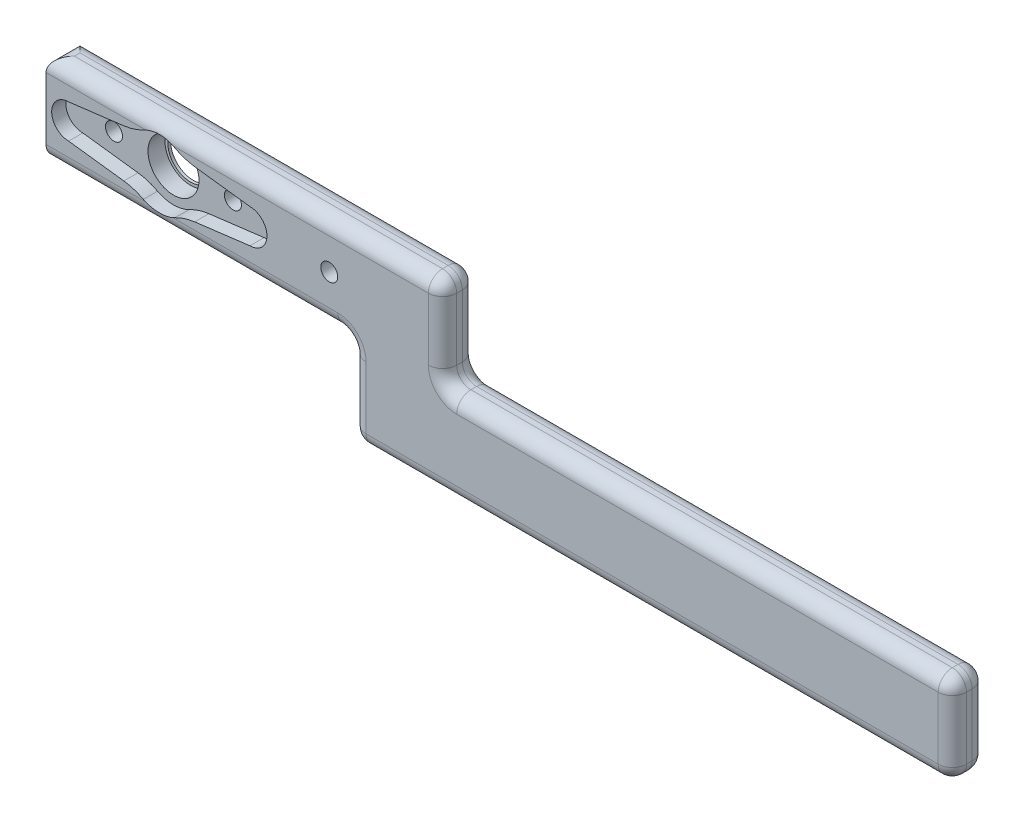
SolidWorks part; units mm, degrees
ref_plane "Спереди" through (0, 0, 0) normal (0, 0, 1) x (1, 0, 0)
ref_plane "Сверху" through (0, 0, 0) normal (0, 1, 0) x (1, 0, 0)
ref_plane "Справа" through (0, 0, 0) normal (1, 0, 0) x (0, 0, -1)
other "Configuration Table"
sketch "Эскиз1" plane through (0, 0, 0) normal (0, 0, 1) x (1, 0, 0)
  line L0 (20, 8) -> (20, 0) construction
  line L2 (0, 0) -> (0, 16)
  line L7 (9.5, 8) -> (0, 8) construction
  line L13 (160, -16) -> (160, 0)
  line L14 (70, 0) -> (160, 0)
  line L15 (54, -16) -> (160, -16)
  line L16 (54, 0) -> (54, -16)
  line L17 (70, 16) -> (70, 0)
  line L18 (0, 16) -> (70, 16)
  line L19 (0, 0) -> (54, 0)
  circle A0 centre (20, 8) radius 1.5
  circle A1 centre (30.5, 8) radius 1.5
  circle A2 centre (9.5, 8) radius 1.5
  dimension "D2" = 3
  dimension "D1" = 70
  dimension "D3" = 20
  dimension "D4" = 21
  dimension "D5" = 90
  dimension "D6" = 16
  dimension "D7" = 16
  dimension "D8" = 16
  dimension "D9" = 54
  dimension "D10" = 106
  dimension "D11" = 16
  dimension "D12" = 90
extrude "Бобышка-Вытянуть1" add sketch "Эскиз1" along normal blind 6
sketch "Эскиз4" plane through (0, 0, 6) normal (0, 0, 1) x (1, 0, 0)
  line L0 (20, 8) -> (20, -10.1424) construction
  line L1 (20, 8) -> (25.9044, 8) construction
  line L2 (4, 11) -> (13.7467, 12.2152)
  line L3 (4, 5) -> (13.7467, 3.7848)
  line L4 (36, 11) -> (26.2533, 12.2152)
  line L5 (36, 5) -> (26.2533, 3.7848)
  arc A0 (17.1911, 2.6981) -> (22.8089, 2.6981) centre (20, 8) ccw
  arc A1 (4, 11) -> (4, 5) centre (4, 8) ccw
  arc A2 (36, 11) -> (36, 5) centre (36, 8) cw
  arc A3 (22.8089, 13.3019) -> (17.1911, 13.3019) centre (20, 8) ccw
  arc A4 (13.7467, 3.7848) -> (17.1911, 2.6981) centre (12.5095, -6.1383) cw
  arc A5 (26.2533, 3.7848) -> (22.8089, 2.6981) centre (27.4905, -6.1383) ccw
  arc A6 (26.2533, 12.2152) -> (22.8089, 13.3019) centre (27.4905, 22.1383) cw
  arc A7 (13.7467, 12.2152) -> (17.1911, 13.3019) centre (12.5095, 22.1383) ccw
  point P1 (1, 8)
  point P4 (39, 8)
  point P18 (16.0314, 3.5)
  point P21 (23.9686, 3.5)
  point P24 (23.9686, 12.5)
  point P27 (16.0314, 12.5)
  dimension "D1" = 12
  dimension "D2" = 6
  dimension "D5" = 10
  dimension "D3" = 38
  dimension "D4" = 9
extrude "Вырез-Вытянуть3" cut sketch "Эскиз4" against normal blind 2.5
sketch "Эскиз5" plane through (0, 0, 3.5) normal (0, 0, 1) x (1, 0, 0)
  circle A0 centre (20, 8) radius 4.5
  dimension "D1" = 9
extrude "Вырез-Вытянуть4" cut sketch "Эскиз5" against normal blind 3
sketch "Эскиз6" plane through (0, 0, 0.5) normal (0, 0, 1) x (1, 0, 0)
  circle A0 centre (20, 8) radius 4
  dimension "D1" = 8
extrude "Вырез-Вытянуть5" cut sketch "Эскиз6" against normal blind 3
sketch "Эскиз7" plane through (0, 0, 6) normal (0, 0, 1) x (1, 0, 0)
  line L0 (50, 8) -> (0, 8) construction
  line L1 (0, 16) -> (0, 0) construction
  circle A0 centre (50, 8) radius 1.5
  circle A1 centre (80, 8) radius 1.5
  circle A2 centre (110, 8) radius 1.5
  circle A3 centre (140, 8) radius 1.5
  circle A4 centre (170, 8) radius 1.5
  dimension "D1" = 3
  dimension "D2" = 50
  dimension "D3" = 5
extrude "Вырез-Вытянуть6" cut sketch "Эскиз7" against normal blind 43
fillet "Скругление1" radius 2.5 19 edges at (27, 0, 6) (27, 0, 0) (70, 8, 6) (70, 8, 0) (70, 16, 3) (35, 16, 6) (0, 16, 3) (35, 16, 0) (54, 0, 3) (54, -8, 6) (54, -8, 0) (54, -16, 3) (107, -16, 6) (160, -16, 3) (107, -16, 0) (160, 0, 3) (115, 0, 6) (70, 0, 3) (115, 0, 0)
fillet "Скругление2" radius 2.5 6 edges at (159.2678, -15.2678, 0.7322) (159.2678, -0.7322, 0.7322) (159.2678, -15.2678, 5.2678) (159.2678, -0.7322, 5.2678) (160, -8, 0) (160, -8, 6)
